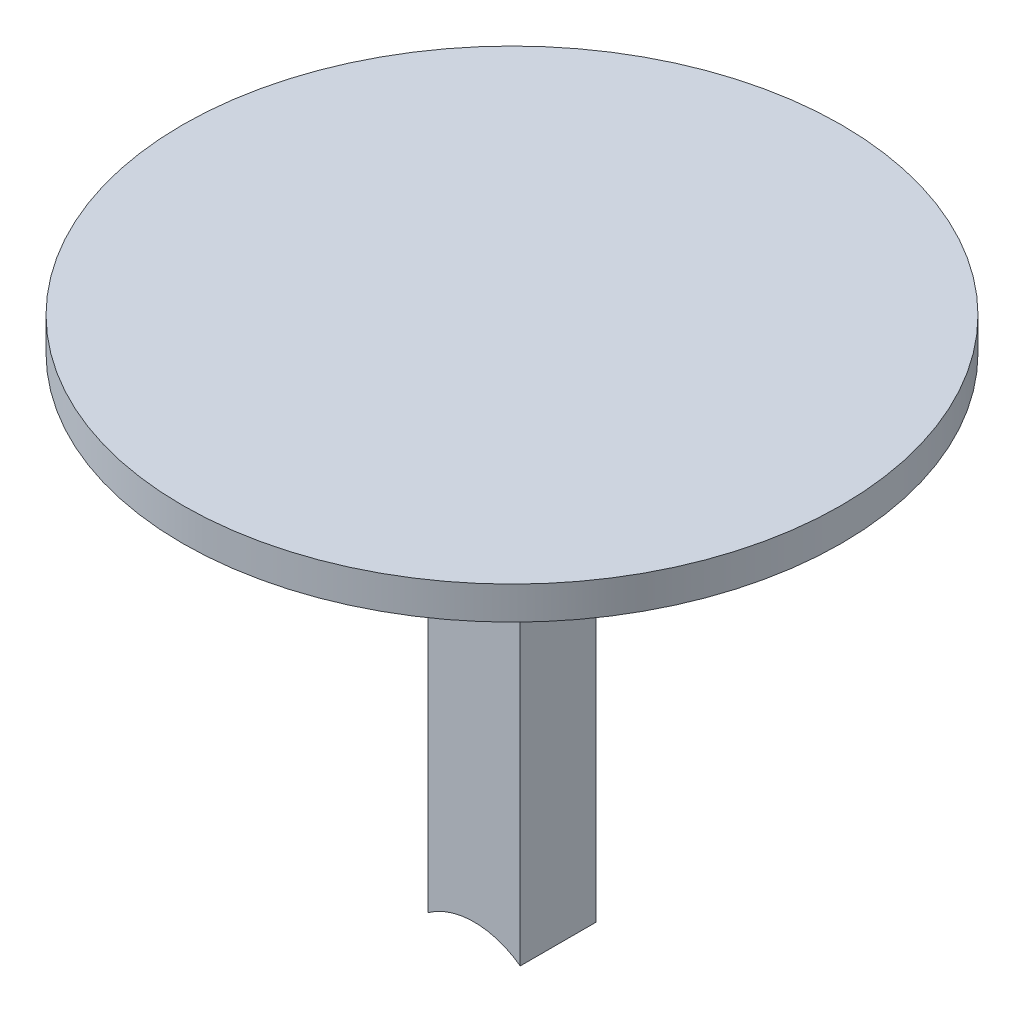
SolidWorks part; units mm, degrees
ref_plane "前视基准面" through (0, 0, 0) normal (0, 0, 1) x (1, 0, 0)
ref_plane "上视基准面" through (0, 0, 0) normal (0, 1, 0) x (1, 0, 0)
ref_plane "右视基准面" through (0, 0, 0) normal (1, 0, 0) x (0, 0, -1)
other "Configuration Table"
sketch "草图1" plane through (0, 0, 0) normal (0, 1, 0) x (1, 0, 0)
  line L0 (0, 4.6) -> (0, -4.6) construction
  line L1 (-2.6, -1.6) -> (2.6, -1.6)
  line L2 (-2.6, -1.6) -> (-2.6, 1.6)
  line L3 (-2.6, 1.6) -> (2.6, 1.6)
  line L4 (2.6, -1.6) -> (2.6, 1.6)
  line L5 (-2.6, -1.6) -> (2.6, 1.6) construction
  line L6 (-2.6, 1.6) -> (2.6, -1.6) construction
  line L7 (-5.6, 4.6) -> (5.6, 4.6)
  line L8 (-5.6, 4.6) -> (-5.6, -4.6)
  line L9 (-5.6, -4.6) -> (5.6, -4.6)
  line L10 (5.6, 4.6) -> (5.6, -4.6)
  point P0 (0, 0)
  point P12 (0, 0)
  dimension "D1" = 3.2
  dimension "D2" = 5.2
  dimension "D3" = 3
  dimension "D4" = 3
extrude "凸台-拉伸1" add sketch "草图1" along normal blind 60 contours L9 L10 L7 L8
extrude "切除-拉伸1" cut sketch "草图1<12>" along normal blind 18 contours L4 L3 L2 L1
sketch "草图1<12>" plane through (0, 0, 0) normal (0, 1, 0) x (1, 0, 0) same geometry as "草图1"
sketch "草图2" plane through (0, 0, -4.6) normal (0, 0, -1) x (-1, 0, 0)
  line L0 (5.6, 0) -> (-5.6, 0) construction
  circle A0 centre (0, -7) radius 9.5
  dimension "D1" = 19
  dimension "D2" = 7
extrude "切除-拉伸2" cut sketch "草图2" against normal through all
fillet "圆角1" radius 2 4 edges at (0, 2.5, -1.6) (-2.6, 2.1373, 0) (2.6, 2.1373, 0) (0, 2.5, 1.6)
sketch "草图3" plane through (0, 60, 0) normal (0, 1, 0) x (1, 0, 0)
  circle A0 centre (0, 0) radius 40
  point P2 (-2.3869, -20.034)
  dimension "D1" = 80
extrude "凸台-拉伸2" add sketch "草图3" along normal blind 4
ref_plane "基准面1" through (0, 0, 0) normal (-1, 0, 0) x (0, 0, 1)
ref_plane "基准面2" through (0, 0, 0) normal (0, 0, 1) x (1, 0, 0)
sketch "草图4" plane through (0, 0, 0) normal (-1, 0, 0) x (0, 0, 1)
  line L0 (-4.6, 60) -> (-4.6, 0.674) construction
  line L1 (-18.2731, 57.5923) -> (-6.2154, 54.2215)
  line L2 (-40, 60) -> (40, 60) construction
  line L3 (-10.5074, 58.95) -> (-7.0614, 39.5625)
  line L4 (-20.1, 60) -> (-4.6, 60)
  line L5 (-4.6, 60) -> (-4.6, 37.5)
  circle A0 centre (-4.6, 40) radius 2.5
  circle A1 centre (-17.6, 60) radius 2.5
  circle A3 centre (-4.6, 60) radius 6
  dimension "D1" = 5
  dimension "D2" = 5
  dimension "D5" = 12
  dimension "D3" = 13
  dimension "D4" = 20
extrude "凸台-拉伸3" add sketch "草图4" along normal mid plane 3 contours L4 A1 | A3 L4 A1 L1 L3 | L4 A3 L5 | A3 L3 L1 | A3 L1 L3 A0 L5 | L5 A0 region at (0, 57.8919, -12.9183) region at (0, 58.939, -17.6) region at (0, 55.8071, -9.2193) region at (0, 48.7604, -6.7355) region at (0, 57.4535, -7.1465) region at (0, 40, -5.661)
sketch "草图5" plane through (0, 0, 0) normal (0, 0, 1) x (1, 0, 0)
  line L0 (-40, 60) -> (40, 60) construction
  line L1 (-5.6, 60) -> (-5.6, 0.674) construction
  line L2 (-21.6645, 57.5646) -> (-6.9548, 54.155)
  line L3 (-11.5074, 58.95) -> (-8.0614, 39.5625)
  line L4 (-23.6, 60) -> (-5.6, 60)
  line L5 (-5.6, 60) -> (-5.6, 37.5)
  circle A0 centre (-21.1, 60) radius 2.5
  circle A1 centre (-5.6, 60) radius 6
  circle A2 centre (-5.6, 40) radius 2.5
  point P18 (-5.2614, 35.1424)
  dimension "D1" = 5
  dimension "D2" = 5
  dimension "D3" = 12
  dimension "D4" = 13
  dimension "D5" = 20
extrude "凸台-拉伸4" add sketch "草图5" along normal mid plane 3 contours L4 A0 | A1 L4 A0 L2 L3 | L4 A1 L5 | A1 L3 L2 | A2 L5 A1 L2 L3 | L5 A2 region at (-14.9901, 57.9024, 0) region at (-21.1, 58.939, 0) region at (-10.1419, 55.6878, 0) region at (-7.7232, 48.7201, 0) region at (-8.1465, 57.4535, 0) region at (-6.661, 40, 0)
mirror "镜向2" about plane through (0, 0, 0) normal (0, 0, 1) of "凸台-拉伸3"
mirror "镜向3" about plane through (0, 0, 0) normal (1, 0, 0) of "凸台-拉伸4"
fillet "圆角2" radius 10 4 edges at (0, 55.2369, -9.8474) (0, 55.2369, 9.8474) (10.8141, 55.0495, 0) (-10.8141, 55.0495, 0)
